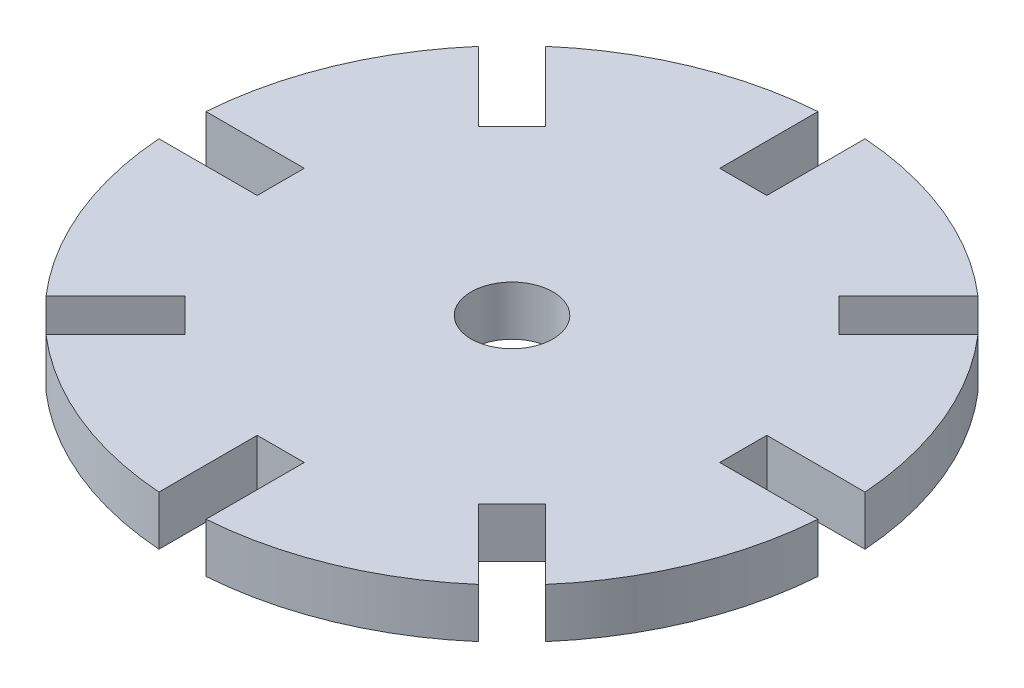
SolidWorks part; units mm, degrees
ref_plane "Front Plane" through (0, 0, 0) normal (0, 0, 1) x (1, 0, 0)
ref_plane "Top Plane" through (0, 0, 0) normal (0, 1, 0) x (1, 0, 0)
ref_plane "Right Plane" through (0, 0, 0) normal (1, 0, 0) x (0, 0, -1)
ref_axis "Axis1" through (0, 1.7463, 0) along (0, -1, 0)
sketch "Sketch1" plane through (0, 0, 0) normal (0, 1, 0) x (1, 0, 0)
  circle A0 centre (0, 0) radius 2.475
  circle A1 centre (0, 0) radius 20
  dimension "D1" = 4.95
  dimension "D2" = 40
extrude "Boss-Extrude1" add sketch "Sketch1" along normal blind 1.5 and the other way blind 1.5
sketch "Sketch2" plane through (0, 1.5, 0) normal (0, 1, 0) x (1, 0, 0)
  line L1 (26, -1.425) -> (14, -1.425)
  line L2 (26, -1.425) -> (26, 1.425)
  line L3 (26, 1.425) -> (14, 1.425)
  line L4 (14, -1.425) -> (14, 1.425)
  line L5 (20, 1.425) -> (20, -1.425) construction
  line L6 (26, 0) -> (14, 0) construction
  line L7 (3.6213, -1.5) -> (3.6213, 1.5) construction
  line L8 (3.6213, 1.5) -> (1.5, 3.6213) construction
  line L9 (1.5, 3.6213) -> (-1.5, 3.6213) construction
  line L10 (-1.5, 3.6213) -> (-3.6213, 1.5) construction
  line L11 (-3.6213, 1.5) -> (-3.6213, -1.5) construction
  line L12 (-3.6213, -1.5) -> (-1.5, -3.6213) construction
  line L13 (-1.5, -3.6213) -> (1.5, -3.6213) construction
  line L14 (1.5, -3.6213) -> (3.6213, -1.5) construction
  circle A0 centre (0, 0) radius 20 construction
  circle A1 centre (0, 0) radius 3.6213 construction
  point P0 (20, 0)
  dimension "D1" = 2.85
  dimension "D2" = 6
  dimension "D3" = 3
extrude "Cut-Extrude1" cut sketch "Sketch2" against normal through all
pattern_circular "CirPattern1" count 8 over 360 about axis through (0, 1.7463, 0) along (0, -1, 0) of "Cut-Extrude1"
